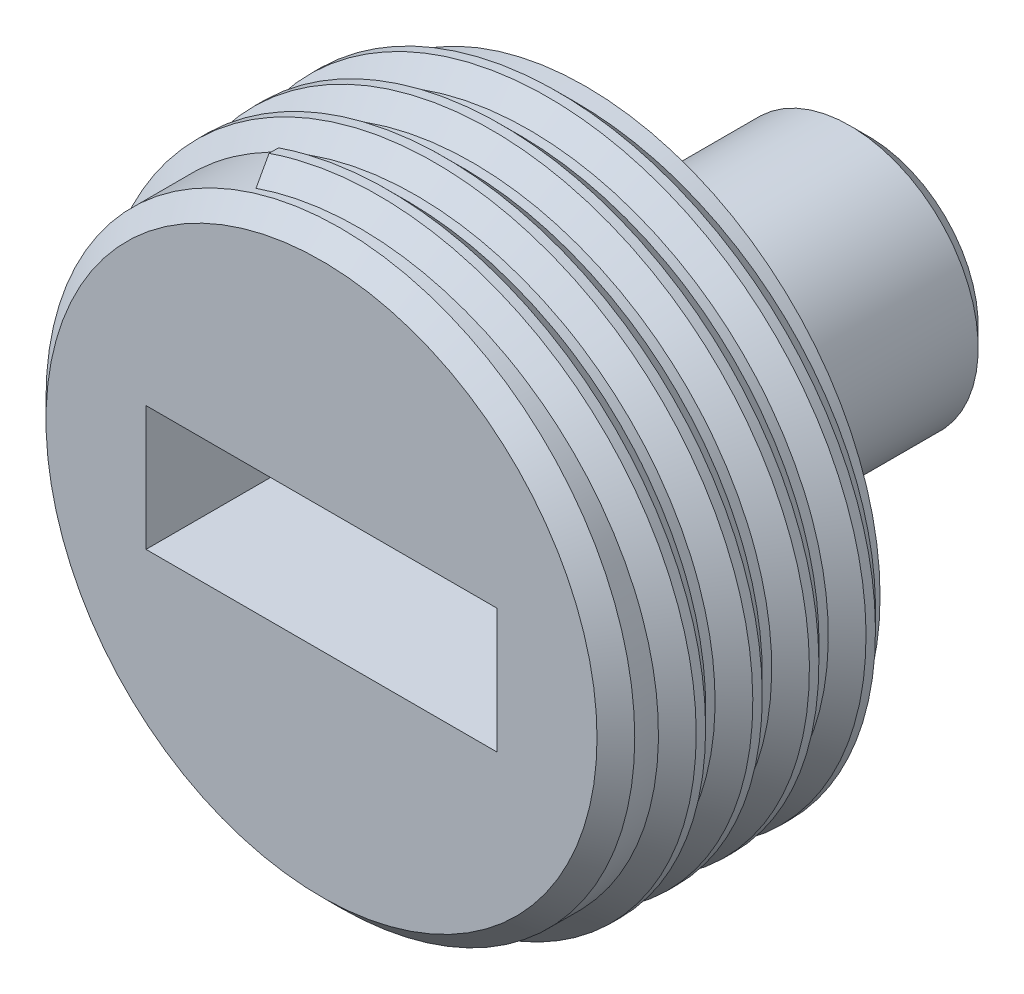
SolidWorks part; units mm, degrees
ref_plane "前视基准面" through (0, 0, 0) normal (0, 0, 1) x (1, 0, 0)
ref_plane "上视基准面" through (0, 0, 0) normal (0, 1, 0) x (1, 0, 0)
ref_plane "右视基准面" through (0, 0, 0) normal (1, 0, 0) x (0, 0, -1)
sketch "草图1" plane through (0, 0, 0) normal (0, 0, 1) x (1, 0, 0)
  circle A1 centre (0, 0) radius 15.6
  dimension "D1" = 31.2
extrude "凸台-拉伸1" add sketch "草图1" along normal blind 10
sketch "草图2" plane through (0, 0, 0) normal (0, 0, -1) x (-1, 0, 0)
  circle A0 centre (0, 0) radius 6.8
  dimension "D1" = 13.6
extrude "凸台-拉伸2" add sketch "草图2" along normal blind 15
sketch "草图6" plane through (0, 0, 0) normal (0, 0, -1) x (-1, 0, 0)
  circle A0 centre (0, 0) radius 6.8 construction
  circle A1 centre (0, 0) radius 6.8
  circle A2 centre (0, 0) radius 19.1268
sketch "草图7" plane through (0, 0, 10) normal (0, 0, 1) x (1, 0, 0)
  circle A0 centre (0, 0) radius 15.6
  dimension "D3" = 31.2
extrude "凸台-拉伸3" add sketch "草图7" along normal blind 4
sketch "草图8" plane through (0, 0, 14) normal (0, 0, 1) x (1, 0, 0)
  line L1 (-9.3, -3.3) -> (9.3, -3.3)
  line L2 (-9.3, -3.3) -> (-9.3, 3.3)
  line L3 (-9.3, 3.3) -> (9.3, 3.3)
  line L4 (9.3, -3.3) -> (9.3, 3.3)
  line L5 (-9.3, -3.3) -> (9.3, 3.3) construction
  line L6 (-9.3, 3.3) -> (9.3, -3.3) construction
  point P0 (0, 0)
  dimension "D1" = 6.6
  dimension "D2" = 18.6
extrude "切除-拉伸3" cut sketch "草图8" against normal blind 10
fillet "圆角1" radius 1 2 edges at (-6.8, 0, -15) (15.6, 0, 14) profile chamfer
chamfer "倒角1" distance 3.2 angle 45 2 edges at (0, 3.3, 4) (0, -3.3, 4)
sketch "草图10" plane through (0, 0, 0) normal (0, 0, -1) x (-1, 0, 0)
  circle A0 centre (0, 0) radius 15.6 construction
  circle A1 centre (0, 0) radius 15.6
curve "螺旋线/涡状线1" pitch 3 height 11.4 radius 15.6 centre (0, 0, 0) axis (0, 0, 1) start towards (-1, 0, 0)
sketch "草图12" plane through (0, 0, 0) normal (0, 1, 0) x (1, 0, 0)
  line L0 (-15.6, 1.25) -> (-15.6, -1.25)
  line L4 (-16.6, 0.25) -> (-15.6, 1.25)
  line L5 (-16.6, -0.25) -> (-16.6, 0.25)
  line L6 (-15.6, -1.25) -> (-16.6, -0.25)
  point P4 (-15.6, 0)
  dimension "D3" = 2.5
sweep "扫描1" add profiles "草图12" path "螺旋线/涡状线1"
extrude "切除-拉伸4" cut sketch "草图6" along normal blind 10
